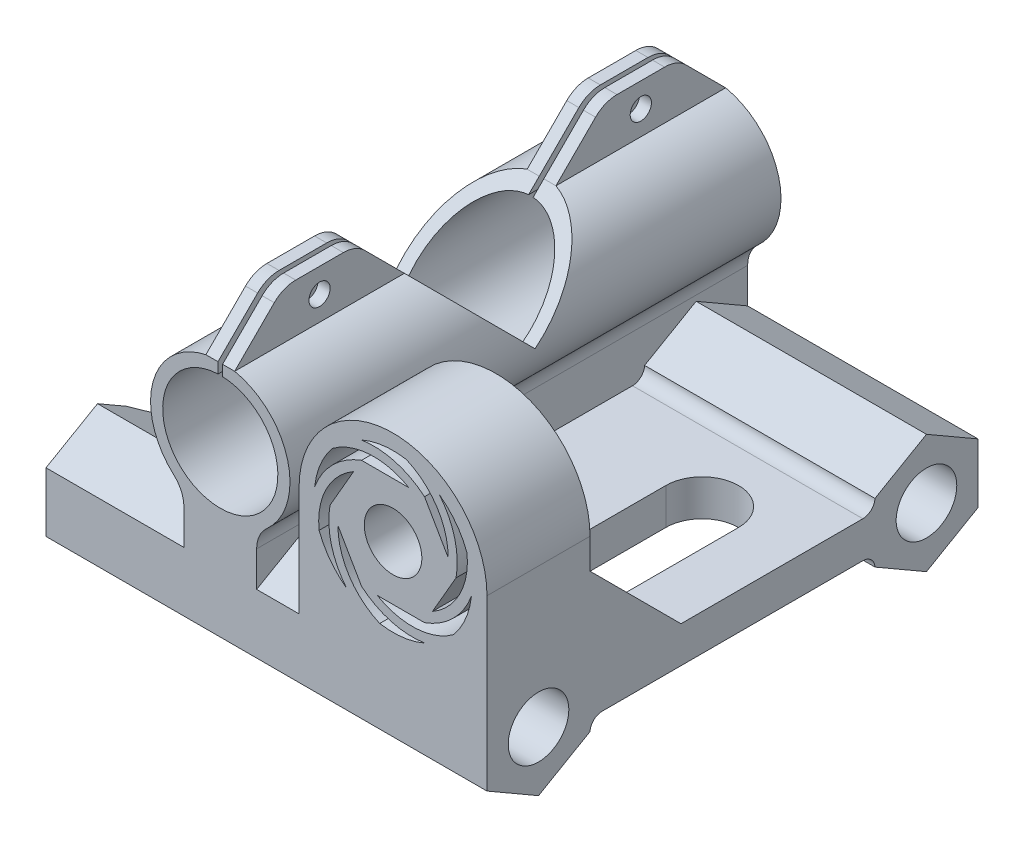
SolidWorks part; units mm, degrees
ref_plane "Front Plane" through (0, 0, 0) normal (0, 0, 1) x (1, 0, 0)
ref_plane "Top Plane" through (0, 0, 0) normal (0, 1, 0) x (1, 0, 0)
ref_plane "Right Plane" through (0, 0, 0) normal (1, 0, 0) x (0, 0, -1)
sketch "Sketch2" plane through (0, 0, 0) normal (1, 0, 0) x (0, 0, -1)
  line L0 (-5.6113, 0) -> (58.3887, 0) construction
  line L1 (2.8887, 3) -> (49.8887, 3)
  line L2 (66.8887, 4.9075) -> (58.3887, 9.815)
  line L3 (58.3887, 9.815) -> (49.8887, 4.9075)
  line L4 (49.8887, 4.9075) -> (49.8887, 3)
  line L5 (49.8887, -4.9075) -> (58.3887, -9.815)
  line L6 (58.3887, -9.815) -> (66.8887, -4.9075)
  line L7 (66.8887, -4.9075) -> (66.8887, 4.9075)
  line L8 (2.8887, 4.9075) -> (-5.6113, 9.815)
  line L9 (-5.6113, 9.815) -> (-14.1113, 4.9075)
  line L10 (-14.1113, 4.9075) -> (-14.1113, -4.9075)
  line L11 (-14.1113, -4.9075) -> (-5.6113, -9.815)
  line L12 (-5.6113, -9.815) -> (2.8887, -4.9075)
  line L13 (2.8887, -4.9075) -> (2.8887, -3)
  line L14 (2.8887, -3) -> (49.8887, -3)
  line L15 (49.8887, -3) -> (49.8887, -4.9075)
  line L16 (2.8887, 3) -> (2.8887, 4.9075)
  circle A2 centre (58.3887, 0) radius 8.5 construction
  circle A3 centre (-5.6113, 0) radius 8.5 construction
  dimension "D2" = 17
  dimension "D3" = 47
  dimension "D4" = 6
  dimension "D5" = 3
extrude "Boss-Extrude1" add sketch "Sketch2" along normal blind 72.75
sketch "Sketch3" plane through (0, 3, 0) normal (0, 1, 0) x (1, 0, 0)
  line L0 (0, 49.8887) -> (47, 2.8887) construction
  line L1 (72.75, 2.8887) -> (0, 2.8887) construction
  line L2 (0, 2.8887) -> (47, 49.8887) construction
  line L3 (72.75, 49.8887) -> (0, 49.8887) construction
  line L4 (72.75, 2.8887) -> (0, 2.8887) construction
  line L5 (1.75, 48.1387) -> (1.75, 2.8887)
  line L6 (39, 41.8887) -> (8, 41.8887) construction
  line L7 (39, 41.8887) -> (39, 10.8887) construction
  line L8 (39, 10.8887) -> (8, 10.8887) construction
  line L9 (8, 41.8887) -> (8, 10.8887) construction
  line L10 (1.75, 48.1387) -> (45.25, 48.1387) construction
  line L11 (45.25, 48.1387) -> (45.25, 4.6387) construction
  line L12 (45.25, 4.6387) -> (1.75, 4.6387) construction
  line L13 (1.75, 2.8887) -> (0, -0.8613)
  line L14 (0, 2.8887) -> (0, -5.6113) construction
  line L16 (1.75, 48.1387) -> (1.75, 49.8887)
  line L18 (1.75, 49.8887) -> (0, 51.6387)
  line L20 (0, 58.3887) -> (0, 49.8887) construction
  line L21 (0, 51.6387) -> (0, -0.8613)
  dimension "D1" = 45
  dimension "D2" = 45
  dimension "D3" = 31
  dimension "D6" = 43.5
extrude "Cut-Extrude1" cut sketch "Sketch3" against normal blind 28 and the other way blind 30
fillet "Fillet3" radius 2 4 edges at (37.25, -3, -2.8887) (37.25, -3, -49.8887) (37.25, 3, -49.8887) (37.25, 3, -2.8887)
sketch "Sketch4" plane through (0, 0, -66.8887) normal (0, 0, -1) x (-1, 0, 0)
  line L0 (-28.75, 3) -> (-28.75, 23) construction
  line L1 (-72.75, 3) -> (-1.75, 3) construction
  line L3 (-34.75, 3) -> (-34.75, 13.1893)
  line L4 (-22.75, 3) -> (-22.75, 13.1893)
  line L5 (-22.75, 3) -> (-34.75, 3)
  line L6 (-26.375, 34.2521) -> (-26.375, 42.2521)
  line L7 (-26.375, 42.2521) -> (-28.375, 42.2521)
  line L8 (-28.375, 42.2521) -> (-28.375, 32.4926)
  line L9 (-31.125, 34.2521) -> (-31.125, 42.2521)
  line L10 (-31.125, 42.2521) -> (-29.125, 42.2521)
  line L11 (-29.125, 42.2521) -> (-29.125, 32.4926)
  line L12 (-1.75, 4.9075) -> (-1.75, -4.9075) construction
  arc A0 (-29.125, 32.4926) -> (-28.375, 32.4926) centre (-28.75, 23) ccw
  arc A1 (-22.75, 13.1893) -> (-26.375, 34.2521) centre (-28.75, 23) ccw
  arc A3 (-31.125, 34.2521) -> (-34.75, 13.1893) centre (-28.75, 23) ccw
  dimension "D1" = 2
  dimension "D2" = 2
  dimension "D3" = 0.75
  dimension "D10" = 8
  dimension "D6" = 19
  dimension "D7" = 23
  dimension "D4" = 12
  dimension "D5" = 6
  dimension "D8" = 20
  dimension "D9" = 0.375
  dimension "D11" = 27
extrude "Boss-Extrude2" add sketch "Sketch4" against normal up to surface (81 mm away) up to face at (36.375, 0, 14.1113)
fillet "Fillet4" radius 5 2 edges at (22.75, 13.1893, -26.3887) (34.75, 13.1893, -26.3887)
sketch "Sketch5" plane through (0, 0, 14.1113) normal (0, 0, -1) x (-1, 0, 0)
  line L0 (-28.75, 23) -> (-110, 23) construction
  line L1 (-72.75, 23) -> (-72.75, 4.9075)
  line L2 (-72.75, 4.9075) -> (-34.75, 4.9075) construction
  line L3 (-72.75, 4.9075) -> (-41.75, 4.9075)
  line L4 (-41.75, 4.9075) -> (-41.75, 23)
  circle A0 centre (-57.25, 23) radius 4.75
  arc A1 (-41.75, 23) -> (-72.75, 23) centre (-57.25, 23) ccw
  arc A2 (-29.125, 32.4926) -> (-28.375, 32.4926) centre (-28.75, 23) ccw construction
  dimension "D1" = 9.5
  dimension "D3" = 31
  dimension "D4" = 0
  dimension "D5" = 28.5
  dimension "D2" = 28.5
extrude "Boss-Extrude7" add sketch "Sketch5" along normal up to vertex (17 mm away) up to point (72.75, 4.9075, -2.8887)
sketch "Sketch6" plane through (0, 0, -2.8887) normal (0, 0, -1) x (-1, 0, 0)
  line L0 (-41.75, 9.815) -> (-34.75, 9.815) construction
  line L1 (-49.7444, 23) -> (-53.4972, 29.5)
  line L2 (-53.4972, 29.5) -> (-61.0028, 29.5)
  line L3 (-61.0028, 29.5) -> (-64.7556, 23)
  line L4 (-64.7556, 23) -> (-61.0028, 16.5)
  line L5 (-61.0028, 16.5) -> (-53.4972, 16.5)
  line L6 (-53.4972, 16.5) -> (-49.7444, 23)
  circle A0 centre (-57.25, 23) radius 6.5 construction
  dimension "D1" = 13
extrude "Cut-Extrude2" cut sketch "Sketch6" against normal blind 7.5
sketch "Sketch7" plane through (0, 0, 0) normal (-1, 0, 0) x (0, 0, 1)
  line L0 (14.1113, 42.2521) -> (-66.8887, 42.2521) construction
  line L1 (-66.8887, 34.2521) -> (-38.8887, 34.2521) construction
  line L2 (-66.8887, 34.2521) -> (-66.8887, 14.4284) construction
  line L3 (-66.8887, 14.4284) -> (-38.8887, 14.4284) construction
  line L4 (-38.8887, 34.2521) -> (-38.8887, 14.4284) construction
  line L6 (14.1113, 14.4284) -> (-13.8887, 14.4284) construction
  line L7 (14.1113, 14.4284) -> (14.1113, 34.2521) construction
  line L8 (14.1113, 34.2521) -> (-13.8887, 34.2521) construction
  line L9 (-13.8887, 14.4284) -> (-13.8887, 34.2521) construction
  line L10 (14.1113, 38.2521) -> (-67.3887, 38.2521) construction
  line L11 (14.1113, 14.4284) -> (14.1113, 34.2521) construction
  line L12 (-38.8887, 42.2521) -> (-66.8887, 42.2521) construction
  line L13 (-52.8887, 34.2521) -> (-52.8887, 42.2521) construction
  line L15 (0.1113, 34.2521) -> (0.1113, 42.2521) construction
  line L16 (-38.8887, 34.2521) -> (-26.3887, 21.7521)
  line L17 (-13.8887, 34.2521) -> (-26.3887, 21.7521)
  line L18 (-13.8887, 34.2521) -> (-13.8887, 42.2521)
  line L19 (-38.8887, 34.2521) -> (-38.8887, 42.2521)
  line L20 (-38.8887, 42.2521) -> (-13.8887, 42.2521)
  line L21 (-66.8887, 14.4284) -> (14.1113, 14.4284) construction
  line L22 (-13.8887, 42.2521) -> (14.1113, 42.2521) construction
  line L25 (14.1113, 42.2521) -> (14.1113, 34.2521) construction
  line L26 (14.1113, 34.2521) -> (-66.8887, 34.2521) construction
  circle A0 centre (0.1113, 38.2521) radius 1.75
  circle A1 centre (-52.8887, 38.2521) radius 1.75
  dimension "D3" = 3.5
  dimension "D1" = 28
  dimension "D2" = 28
  dimension "D4" = 45
  dimension "D5" = 45
extrude "Cut-Extrude3" cut sketch "Sketch7" against normal up to surface (41.75 mm away) up to face at (41.75, 13.126, 5.6113)
chamfer "Chamfer1" distance 8 angle 45 8 edges at (27.375, 42.2521, -66.8887) (30.125, 42.2521, -66.8887) (30.125, 42.2521, -38.8887) (27.375, 42.2521, -38.8887) (30.125, 42.2521, 14.1113) (27.375, 42.2521, 14.1113) (27.375, 42.2521, -13.8887) (30.125, 42.2521, -13.8887)
fillet "Fillet5" radius 5 8 edges at (27.375, 42.2521, 6.1113) (30.125, 42.2521, 6.1113) (30.125, 42.2521, -5.8887) (27.375, 42.2521, -5.8887) (27.375, 42.2521, -46.8887) (30.125, 42.2521, -46.8887) (30.125, 42.2521, -58.8887) (27.375, 42.2521, -58.8887)
sketch "Sketch9" plane through (72.75, 0, 0) normal (1, 0, 0) x (0, 0, -1)
  line L0 (-9.8613, 7.3612) -> (-1.3613, -7.3612) construction
  line L1 (-5.6113, 9.815) -> (-14.1113, 4.9075) construction
  line L2 (-5.6113, -9.815) -> (2.8887, -4.9075) construction
  line L3 (54.1387, -7.3612) -> (62.6387, 7.3612) construction
  line L4 (49.8887, -4.9075) -> (58.3887, -9.815) construction
  circle A0 centre (58.3887, 0) radius 5
  circle A1 centre (-5.6113, 0) radius 5
  dimension "D1" = 10
extrude "Cut-Extrude5" cut sketch "Sketch9" against normal up to surface (50 mm away) up to face at (22.75, 6.5862, -26.3887)
sketch "Sketch14" plane through (0, 3, 0) normal (0, 1, 0) x (1, 0, 0)
  line L0 (57.75, 64.8887) -> (57.75, -14.1113) construction
  line L3 (72.75, 47.8909) -> (72.75, 4.8866) construction
  line L4 (57.75, 36.3887) -> (57.75, 14.3887) construction
  line L5 (63.75, 36.3887) -> (63.75, 14.3887)
  line L6 (51.75, 36.3887) -> (51.75, 14.3887)
  line L8 (41.75, -14.1113) -> (34.75, -14.1113) construction
  arc A0 (63.75, 36.3887) -> (51.75, 36.3887) centre (57.75, 36.3887) ccw
  arc A1 (51.75, 14.3887) -> (63.75, 14.3887) centre (57.75, 14.3887) ccw
  point P10 (57.75, 25.3887)
  dimension "D2" = 6
  dimension "D1" = 15
  dimension "D3" = 22
extrude "Cut-Extrude8" cut sketch "Sketch14" against normal blind 10
sketch "Sketch18" plane through (72.75, 0, 0) normal (1, 0, 0) x (0, 0, -1)
  line L0 (2.8941, 18) -> (2.8941, 3)
  line L1 (2.8941, 3) -> (17.8941, 3)
  line L2 (47.8909, 3) -> (4.8866, 3) construction
  line L3 (17.8941, 3) -> (2.8941, 18)
  dimension "D1" = 15
extrude "Boss-Extrude10" add sketch "Sketch18" against normal blind 3.5
sketch "Sketch19" plane through (41.75, 0, 0) normal (-1, 0, 0) x (0, 0, 1)
  line L0 (-2.8941, 18) -> (-17.8941, 3)
  line L1 (-17.8941, 3) -> (-2.8887, 3)
  line L2 (-2.8887, 4.9075) -> (-2.8887, -4.9075) construction
  line L3 (-2.8887, 3) -> (-2.8941, 18)
extrude "Boss-Extrude11" add sketch "Sketch19" against normal blind 3.5
sketch "Sketch20" plane through (0, 0, -2.8887) normal (0, 0, -1) x (-1, 0, 0)
  line L0 (-53.4972, 29.5) -> (-61.0028, 29.5) construction
  line L1 (-46.8577, 23) -> (-52.0538, 32) construction
  line L2 (-52.0538, 32) -> (-62.4462, 32) construction
  line L3 (-62.4462, 32) -> (-67.6423, 23) construction
  line L4 (-67.6423, 23) -> (-62.4462, 14) construction
  line L5 (-62.4462, 14) -> (-52.0538, 14) construction
  line L6 (-52.0538, 14) -> (-46.8577, 23) construction
  line L7 (-67.6423, 23) -> (-63.7454, 16.2504)
  line L8 (-62.4462, 14) -> (-54.6524, 14)
  line L9 (-52.0538, 14) -> (-48.157, 20.7496)
  line L10 (-46.8577, 23) -> (-50.7546, 29.7496)
  line L11 (-52.0538, 32) -> (-59.8476, 32)
  line L12 (-62.4462, 32) -> (-66.343, 25.2504)
  arc A0 (-64.9054, 33.5069) -> (-69.4463, 27.5) centre (-57.25, 23) ccw construction
  arc A1 (-41.75, 23) -> (-72.75, 23) centre (-57.25, 23) ccw construction
  circle A2 centre (-57.25, 23) radius 9 construction
  arc A3 (-52.0538, 32) -> (-44.3231, 24.3763) centre (-56.4825, 19.7776) cw
  arc A4 (-50.7546, 29.7496) -> (-45.0537, 18.5) centre (-56.4825, 19.7776) cw
  arc A5 (-52.5648, 30.5897) -> (-45.7261, 23.8457) centre (-56.4825, 19.7776) cw construction
  arc A6 (-48.157, 20.7496) -> (-55.049, 10.1877) centre (-59.6569, 20.7241) cw
  arc A7 (-46.8577, 23) -> (-49.5946, 12.4931) centre (-59.6569, 20.7241) cw
  arc A8 (-54.6524, 14) -> (-67.2453, 14.6877) centre (-60.4244, 23.9465) cw
  arc A9 (-52.0538, 14) -> (-62.5216, 11.1168) centre (-60.4244, 23.9465) cw
  arc A10 (-63.7454, 16.2504) -> (-69.4463, 27.5) centre (-58.0175, 26.2224) cw
  arc A11 (-62.4462, 14) -> (-70.1769, 21.6237) centre (-58.0175, 26.2224) cw
  arc A12 (-66.343, 25.2504) -> (-59.451, 35.8123) centre (-54.8431, 25.2759) cw
  arc A13 (-67.6423, 23) -> (-64.9054, 33.5069) centre (-54.8431, 25.2759) cw
  arc A14 (-59.8476, 32) -> (-47.2547, 31.3123) centre (-54.0756, 22.0535) cw
  arc A15 (-62.4462, 32) -> (-51.9784, 34.8832) centre (-54.0756, 22.0535) cw
  arc A16 (-64.9054, 33.5069) -> (-69.4463, 27.5) centre (-57.25, 23) ccw
  arc A17 (-70.1769, 21.6237) -> (-67.2453, 14.6877) centre (-57.25, 23) ccw construction
  arc A18 (-70.1769, 21.6237) -> (-67.2453, 14.6877) centre (-57.25, 23) ccw
  arc A19 (-62.5216, 11.1168) -> (-55.049, 10.1877) centre (-57.25, 23) ccw construction
  arc A20 (-62.5216, 11.1168) -> (-55.049, 10.1877) centre (-57.25, 23) ccw
  arc A21 (-49.5946, 12.4931) -> (-45.0537, 18.5) centre (-57.25, 23) ccw construction
  arc A22 (-49.5946, 12.4931) -> (-45.0537, 18.5) centre (-57.25, 23) ccw
  arc A23 (-44.3231, 24.3763) -> (-47.2547, 31.3123) centre (-57.25, 23) ccw construction
  arc A24 (-44.3231, 24.3763) -> (-47.2547, 31.3123) centre (-57.25, 23) ccw
  arc A25 (-51.9784, 34.8832) -> (-59.451, 35.8123) centre (-57.25, 23) ccw construction
  arc A26 (-51.9784, 34.8832) -> (-59.451, 35.8123) centre (-57.25, 23) ccw
  point P55 (-57.25, 23)
  dimension "D1" = 2.5
  dimension "D5" = 6
  dimension "D6" = 11.5
  dimension "D2" = 2.5
  dimension "D4" = 4.5
  dimension "D3" = 1.5
extrude "Cut-Extrude9" cut sketch "Sketch20" against normal up to surface (17 mm away) up to face at (31.8889, 17.1213, 14.1113)
